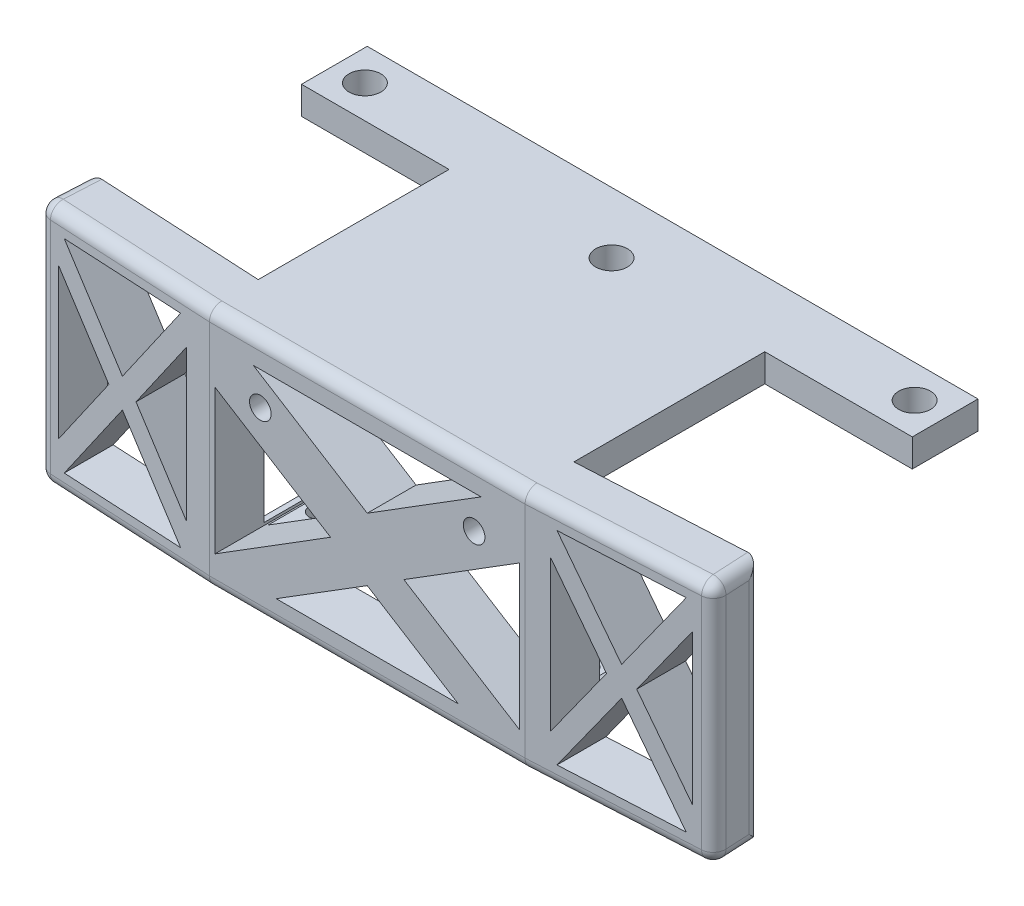
SolidWorks part; units mm, degrees
ref_plane "Front Plane" through (0, 0, 0) normal (0, 0, 1) x (1, 0, 0)
ref_plane "Top Plane" through (0, 0, 0) normal (0, 1, 0) x (1, 0, 0)
ref_plane "Right Plane" through (0, 0, 0) normal (1, 0, 0) x (0, 0, -1)
sketch "Sketch1" plane through (0, 0, 0) normal (0, 1, 0) x (1, 0, 0)
  line L0 (25.846, 6) -> (25.846, 0) construction
  line L1 (0, 0) -> (51.692, 0)
  line L2 (0, 0) -> (0, 12)
  line L3 (0, 12) -> (51.692, 12)
  line L4 (51.692, 0) -> (51.692, 12)
  circle A1 centre (3.846, 6) radius 1.5
  circle A2 centre (47.846, 6) radius 1.5
  point P7 (25.846, 0)
  point P8 (0, 6)
  dimension "D1" = 6
  dimension "D2" = 3
  dimension "D3" = 22
extrude "Boss-Extrude1" add sketch "Sketch1" along normal blind 6
sketch "Sketch2" plane through (0, 0, 0) normal (0, 0, 1) x (1, 0, 0)
  line L0 (51.692, 6) -> (51.692, 0) construction
  line L1 (0, 0) -> (51.692, 0)
  line L2 (0, 0) -> (0, 35)
  line L3 (0, 35) -> (51.692, 35)
  line L4 (51.692, 0) -> (51.692, 35)
  line L5 (25.846, 0) -> (25.846, 35) construction
  circle A0 centre (8.346, 30) radius 1.7701
  circle A1 centre (43.346, 30) radius 1.7701
  dimension "D1" = 35
  dimension "D2" = 30
  dimension "D3" = 17.5
extrude "Boss-Extrude2" add sketch "Sketch2" along normal blind 8
sketch "Sketch3" plane through (0, 0, 0) normal (0, -1, 0) x (1, 0, 0)
  circle A0 centre (47.846, -6) radius 2.25
  circle A1 centre (3.846, -6) radius 2.25
  dimension "D1" = 4.5
extrude "Cut-Extrude1" cut sketch "Sketch3" against normal blind 2
sketch "Sketch4" plane through (0, 0, 0) normal (0, 0, -1) x (-1, 0, 0)
  circle A0 centre (-43.346, 30) radius 2.25
  circle A1 centre (-8.346, 30) radius 2.25
  dimension "D1" = 4.5
extrude "Cut-Extrude2" cut sketch "Sketch4" against normal blind 2
sketch "Sketch5" plane through (0, 35, 0) normal (0, 1, 0) x (1, 0, 0)
  line L0 (25.846, 32) -> (25.846, -8) construction
  line L1 (0, -8) -> (51.692, -8)
  line L2 (0, -8) -> (0, 42)
  line L3 (0, 42) -> (51.692, 42)
  line L4 (51.692, -8) -> (51.692, 42)
  line L5 (0, 42) -> (-24.154, 42)
  line L6 (0, 42) -> (0, 31.2412)
  line L7 (0, 31.2412) -> (-24.154, 31.2412)
  line L8 (-24.154, 42) -> (-24.154, 31.2412)
  line L9 (51.692, 31.2412) -> (75.846, 31.2412)
  line L10 (75.846, 42) -> (75.846, 31.2412)
  line L11 (51.692, 42) -> (75.846, 42)
  line L12 (51.692, 42) -> (51.692, 31.2412)
  circle A0 centre (25.846, 32) radius 2.5
  point P8 (25.846, 42)
  dimension "D1" = 5
  dimension "D2" = 40
  dimension "D3" = 50
  dimension "D4" = 100
  dimension "D5" = 51.692
extrude "Boss-Extrude3" add sketch "Sketch5" along normal blind 5 and the other way blind 0.0001
sketch "Sketch14" plane through (0, 0, 8) normal (0, 0, 1) x (1, 0, 0)
  line L0 (50.7751, 29.208) -> (50.7751, 5.5695)
  line L1 (50.7751, 5.5695) -> (31.846, 17.3888)
  line L2 (31.846, 17.3888) -> (50.7751, 29.208)
  line L3 (19.846, 17.3888) -> (0.9168, 5.5695)
  line L4 (0.9168, 5.5695) -> (0.9168, 29.208)
  line L5 (0.9168, 29.208) -> (19.846, 17.3888)
  line L6 (25.846, 23.7992) -> (44.4859, 35.4379)
  line L7 (25.846, 23.7992) -> (7.206, 35.4379)
  line L8 (7.206, 35.4379) -> (44.4859, 35.4379)
  line L10 (25.846, 13.5325) -> (10.9433, 4.2273)
  line L11 (25.846, 13.5325) -> (40.7487, 4.2273)
  line L12 (40.7487, 4.2273) -> (10.9433, 4.2273)
  dimension "D2" = 12
extrude "Cut-Extrude5" cut sketch "Sketch14" against normal blind 54
sketch "Sketch15" plane through (0, 0, 0) normal (0, -1, 0) x (1, 0, 0)
  line L1 (10.14, -12) -> (43.5295, -12)
  line L2 (10.14, -12) -> (10.14, -0.065)
  line L3 (10.14, -0.065) -> (43.5295, -0.065)
  line L4 (43.5295, -12) -> (43.5295, -0.065)
  line L6 (18.7579, -12) -> (33.809, -12)
  line L7 (18.7579, -12) -> (18.7579, -20.2236)
  line L8 (18.7579, -20.2236) -> (33.809, -20.2236)
  line L9 (33.809, -12) -> (33.809, -20.2236)
extrude "Cut-Extrude6" cut sketch "Sketch15" against normal blind 31
sketch "Sketch20" plane through (0, 40, 0) normal (0, 1, 0) x (1, 0, 0)
  line L0 (0, -8) -> (-29.4569, -6.4562)
  line L3 (0, 0) -> (-29.0388, 1.5219)
  line L4 (-29.0388, 1.5219) -> (-29.4569, -6.4562)
  line L5 (0, 0) -> (0, -8)
  line L6 (25.846, 32) -> (25.846, -8) construction
  line L7 (51.692, 0) -> (51.692, -8)
  line L8 (80.7308, 1.5219) -> (81.1489, -6.4562)
  line L9 (51.692, 0) -> (80.7308, 1.5219)
  line L10 (51.692, -8) -> (81.1489, -6.4562)
extrude "Boss-Extrude6" add sketch "Sketch20" against normal up to surface (40 mm away) up to face at (47.846, 0, -8.25)
sketch "Sketch21" plane through (0, 0, 8) normal (0, 0, 1) x (1, 0, 0)
  line L0 (-3.9661, 7.6786) -> (-3.9661, 32.3214)
  line L1 (-3.9661, 32.3214) -> (-12.6696, 20)
  line L2 (-12.6696, 20) -> (-3.9661, 7.6786)
  line L3 (-4.9658, 36.622) -> (-15.0183, 22.3909)
  line L4 (-15.0183, 22.3909) -> (-25.0707, 36.622)
  line L5 (-25.0707, 36.622) -> (-4.9658, 36.622)
  line L6 (-15.0183, 22.3909) -> (-15.0183, 36.622) construction
  line L7 (-12.6696, 20) -> (-3.9661, 20) construction
  line L8 (25.846, 23.7992) -> (25.846, 40) construction
  line L10 (-15.0183, 17.6091) -> (-25.0707, 3.378)
  line L11 (-4.9658, 3.378) -> (-15.0183, 17.6091)
  line L12 (-25.0707, 3.378) -> (-4.9658, 3.378)
  line L13 (-26.0704, 32.3214) -> (-17.3669, 20)
  line L14 (-26.0704, 7.6786) -> (-26.0704, 32.3214)
  line L15 (-17.3669, 20) -> (-26.0704, 7.6786)
  line L16 (0, 40) -> (0, 0) construction
  line L17 (64.3616, 20) -> (55.6581, 20) construction
  line L18 (66.7102, 22.3909) -> (66.7102, 36.622) construction
  line L19 (69.0588, 20) -> (77.7623, 7.6786)
  line L20 (77.7623, 7.6786) -> (77.7623, 32.3214)
  line L21 (77.7623, 32.3214) -> (69.0588, 20)
  line L22 (76.7627, 3.378) -> (56.6577, 3.378)
  line L23 (56.6577, 3.378) -> (66.7102, 17.6091)
  line L24 (66.7102, 17.6091) -> (76.7627, 3.378)
  line L25 (76.7627, 36.622) -> (56.6577, 36.622)
  line L26 (66.7102, 22.3909) -> (76.7627, 36.622)
  line L27 (56.6577, 36.622) -> (66.7102, 22.3909)
  line L28 (64.3616, 20) -> (55.6581, 7.6786)
  line L29 (55.6581, 32.3214) -> (64.3616, 20)
  line L30 (55.6581, 7.6786) -> (55.6581, 32.3214)
  point P23 (0, 20)
extrude "Cut-Extrude8" cut sketch "Sketch21" against normal blind 31
fillet "Fillet1" radius 2 13 edges at (80.7308, 20, -1.5219) (-14.7285, 0, 7.2281) (-14.7285, 40, 7.2281) (-29.4569, 20, 6.4562) (66.4204, 0, 7.2281) (66.4204, 40, 7.2281) (-29.0388, 20, -1.5219) (25.846, 0, 8) (81.1489, 20, 6.4562) (-29.2479, 0, 2.4672) (-29.2479, 40, 2.4672) (80.9398, 0, 2.4672) (80.9398, 40, 2.4672)
sketch "Sketch23" plane through (0, 40, 0) normal (0, 1, 0) x (1, 0, 0)
  line L0 (-24.154, 42) -> (-24.154, 31.2412) construction
  line L1 (25.846, 32) -> (25.846, 42) construction
  line L2 (75.846, 42) -> (-24.154, 42) construction
  circle A0 centre (-19.154, 36.6206) radius 2.6
  circle A2 centre (25.846, 32) radius 2.6
  circle A3 centre (70.846, 36.6206) radius 2.6
  point P10 (-24.154, 36.6206)
  dimension "D1" = 5.2
  dimension "D2" = 45
extrude "Cut-Extrude9" cut sketch "Sketch23" against normal blind 31
sketch "Sketch25" plane through (0, 34.9999, 0) normal (0, -1, 0) x (1, 0, 0)
  line L0 (51.692, 0) -> (51.692, -31.2412) construction
  line L1 (-24.154, -42) -> (85.2823, -42)
  line L2 (-24.154, -42) -> (-24.154, -2.4952)
  line L3 (-24.154, -2.4952) -> (85.2823, -2.4952)
  line L4 (85.2823, -42) -> (85.2823, -2.4952)
  line L5 (0, 0) -> (51.692, 0)
  line L6 (0, 0) -> (0, -2.4952)
  line L7 (0, -2.4952) -> (51.692, -2.4952)
  line L8 (51.692, 0) -> (51.692, -2.4952)
extrude "Cut-Extrude10" cut sketch "Sketch25" against normal up to surface (0.438 mm away) up to face at (25.846, 35.4379, -29.4)
